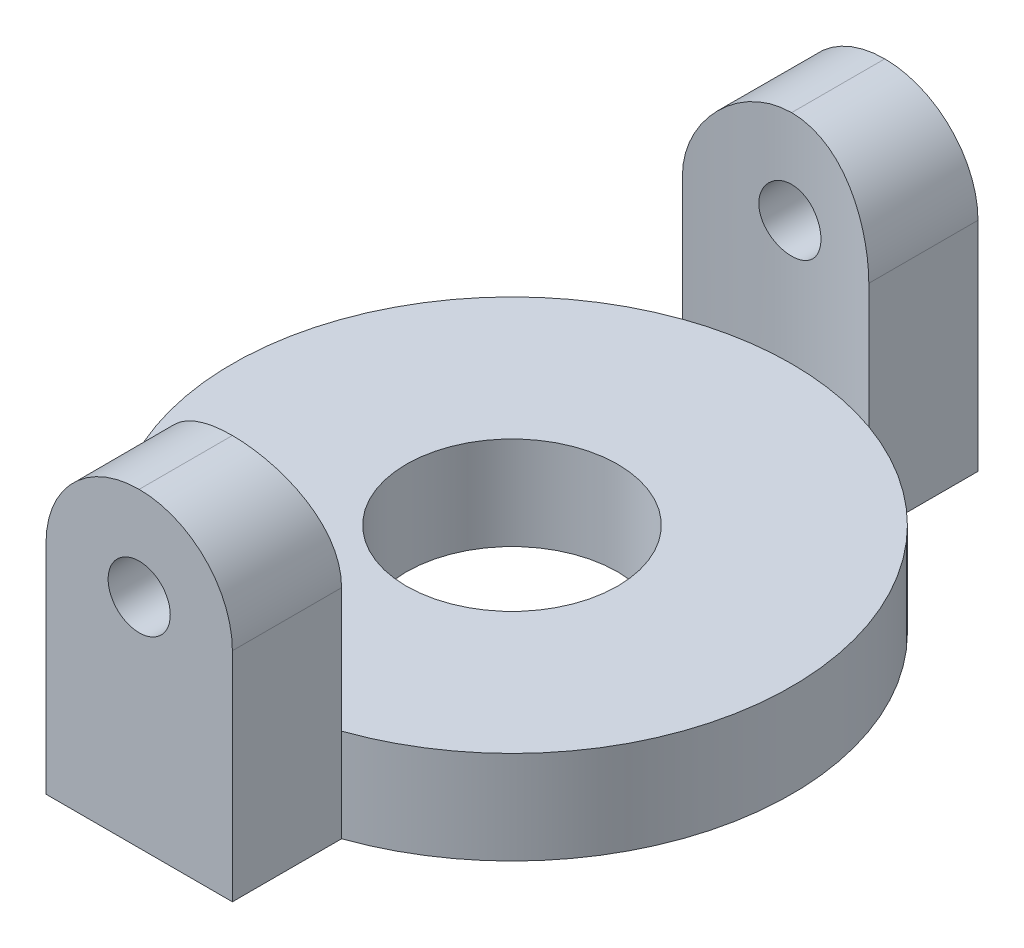
SolidWorks part; units mm, degrees
ref_plane "Front Plane" through (0, 0, 0) normal (0, 0, 1) x (1, 0, 0)
ref_plane "Top Plane" through (0, 0, 0) normal (0, 1, 0) x (1, 0, 0)
ref_plane "Right Plane" through (0, 0, 0) normal (1, 0, 0) x (0, 0, -1)
sketch "Sketch1" plane through (0, 0, 0) normal (0, 1, 0) x (1, 0, 0)
  circle A0 centre (0, 0) radius 4.5
  circle A1 centre (0, 0) radius 1.7
  dimension "D1" = 3.4
  dimension "D2" = 9
extrude "Boss-Extrude1" add sketch "Sketch1" along normal blind 1.5
sketch "Sketch2" plane through (0, 1.5, 0) normal (0, 1, 0) x (1, 0, 0)
  line L1 (3.1754, 0) -> (1.5877, 2.75)
  line L2 (1.5877, 2.75) -> (-1.5877, 2.75)
  line L3 (-1.5877, 2.75) -> (-3.1754, 0)
  line L4 (-3.1754, 0) -> (-1.5877, -2.75)
  line L5 (-1.5877, -2.75) -> (1.5877, -2.75)
  line L6 (1.5877, -2.75) -> (3.1754, 0)
  circle A0 centre (0, 0) radius 2.75 construction
  dimension "D1" = 5.5
sketch "Sketch3" plane through (0, 0, 0) normal (0, 1, 0) x (1, 0, 0)
  line L0 (-1.5, -4.2426) -> (-1.5, -6)
  line L1 (-1.5, 6) -> (1.5, 6)
  line L2 (-1.5, 6) -> (-1.5, 4.2426)
  line L3 (-1.5, -6) -> (1.5, -6)
  line L4 (1.5, 6) -> (1.5, 4.2426)
  line L5 (-1.5, 6) -> (1.5, -6) construction
  line L6 (-1.5, -6) -> (1.5, 6) construction
  line L7 (1.5, -4.2426) -> (1.5, -6)
  circle A0 centre (0, 0) radius 4.5 construction
  arc A1 (-1.5, 4.2426) -> (1.5, 4.2426) centre (0, 0) cw
  arc A2 (-1.5, -4.2426) -> (1.5, -4.2426) centre (0, 0) ccw
  point P0 (0, 0)
  dimension "D1" = 6
  dimension "D2" = 3
extrude "Boss-Extrude2" add sketch "Sketch3" along normal blind 5
sketch "Sketch4" plane through (0, 0, 6) normal (0, 0, 1) x (1, 0, 0)
  line L0 (-1.5, 5) -> (1.5, 5) construction
  line L1 (-1.5, 5) -> (-1.5, 0) construction
  circle A0 centre (0, 3.5) radius 0.5
  dimension "D1" = 1
  dimension "D2" = 1.5
  dimension "D3" = 1.5
extrude "Cut-Extrude1" cut sketch "Sketch4" against normal through all
fillet "Fillet1" radius 1.5 4 edges at (1.5, 5, 5.1213) (-1.5, 5, 5.1213) (1.5, 5, -5.1213) (-1.5, 5, -5.1213)
